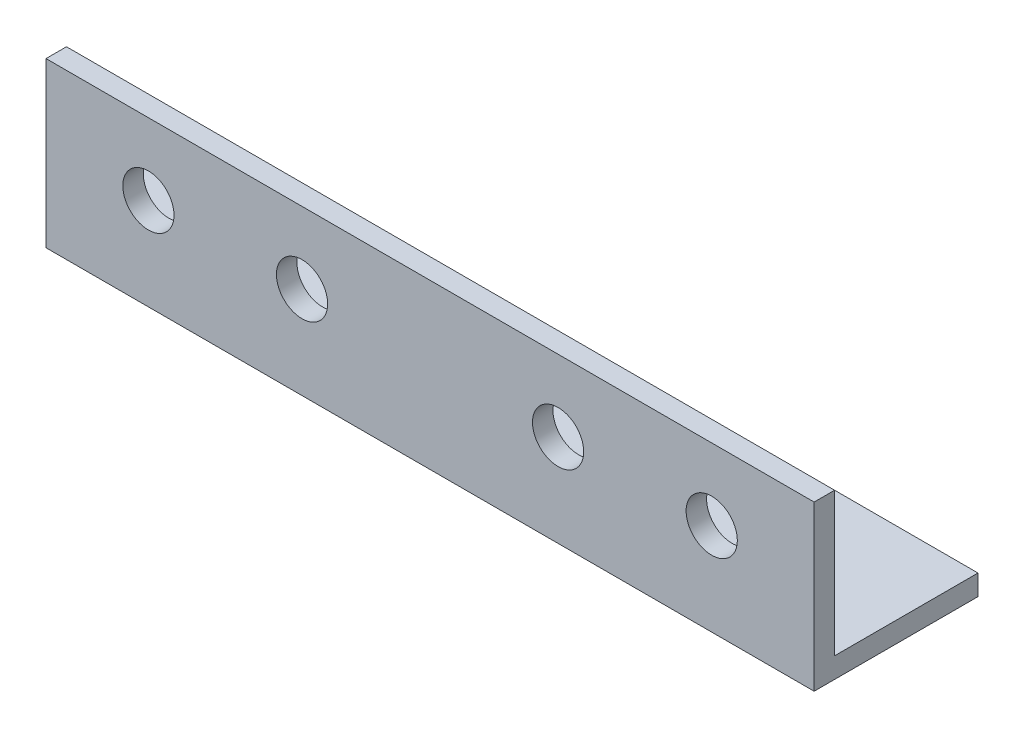
SolidWorks part; units mm, degrees
ref_plane "Спереди" through (0, 0, 0) normal (0, 0, 1) x (1, 0, 0)
ref_plane "Сверху" through (0, 0, 0) normal (0, 1, 0) x (1, 0, 0)
ref_plane "Справа" through (0, 0, 0) normal (1, 0, 0) x (0, 0, -1)
sketch "Эскиз1" plane through (0, 0, 0) normal (1, 0, 0) x (0, 0, -1)
  line L0 (0, 32) -> (0, 0)
  line L1 (0, 0) -> (32, 0)
extrude "Вытянуть-Тонкостенный1" add sketch "Эскиз1" along normal blind 150 thin thin type one direction reverse wall 4
sketch "Эскиз2" plane through (0, 0, -4) normal (0, 0, -1) x (-1, 0, 0)
  line L0 (-75, 38.0477) -> (-75, -6) construction
  circle A0 centre (-130, 18) radius 5
  circle A1 centre (-100, 18) radius 5
  circle A2 centre (-50, 18) radius 5
  circle A3 centre (-20, 18) radius 5
  dimension "D1" = 2
extrude "Вырез-Вытянуть1" cut sketch "Эскиз2" against normal through all
